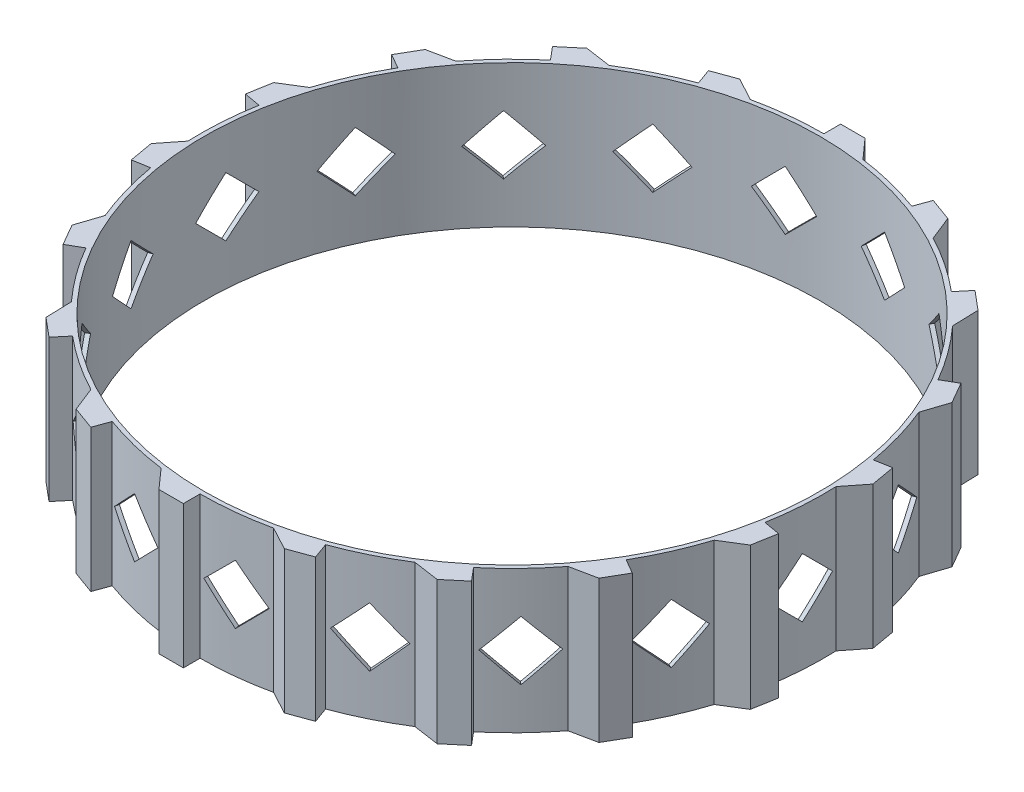
SolidWorks part; units mm, degrees
ref_plane "Front Plane" through (0, 0, 0) normal (0, 0, 1) x (1, 0, 0)
ref_plane "Top Plane" through (0, 0, 0) normal (0, 1, 0) x (1, 0, 0)
ref_plane "Right Plane" through (0, 0, 0) normal (1, 0, 0) x (0, 0, -1)
sketch "Sketch1" plane through (0, 0, 0) normal (0, 1, 0) x (1, 0, 0)
  line L2 (0, 37.25) -> (0, 39.25)
  line L3 (0, 39.25) -> (2.9158, 39.25)
  line L4 (2.9158, 39.25) -> (5, 36.9129)
  line L5 (12.7403, 35.0036) -> (13.4243, 36.8829)
  line L6 (13.4243, 36.8829) -> (16.1643, 35.8857)
  line L7 (16.1643, 35.8857) -> (17.3234, 32.9767)
  line L8 (23.9438, 28.5352) -> (25.2294, 30.0672)
  line L9 (25.2294, 30.0672) -> (27.4631, 28.193)
  line L10 (27.4631, 28.193) -> (27.5574, 25.063)
  line L11 (32.2594, 18.625) -> (33.9915, 19.625)
  line L12 (33.9915, 19.625) -> (35.4494, 17.0998)
  line L13 (35.4494, 17.0998) -> (34.4675, 14.1263)
  line L14 (36.6841, 6.4684) -> (38.6537, 6.8157)
  line L15 (38.6537, 6.8157) -> (39.16, 3.9442)
  line L16 (39.16, 3.9442) -> (37.2204, 1.4858)
  line L17 (36.6841, -6.4684) -> (38.6537, -6.8157)
  line L18 (38.6537, -6.8157) -> (38.1474, -9.6872)
  line L19 (38.1474, -9.6872) -> (35.4839, -11.3339)
  line L20 (32.2594, -18.625) -> (33.9915, -19.625)
  line L21 (33.9915, -19.625) -> (32.5336, -22.1502)
  line L22 (32.5336, -22.1502) -> (29.4675, -22.7866)
  line L23 (23.9438, -28.5352) -> (25.2294, -30.0672)
  line L24 (25.2294, -30.0672) -> (22.9958, -31.9415)
  line L25 (22.9958, -31.9415) -> (19.8969, -31.4909)
  line L26 (12.7403, -35.0036) -> (13.4243, -36.8829)
  line L27 (13.4243, -36.8829) -> (10.6843, -37.8802)
  line L28 (10.6843, -37.8802) -> (7.9265, -36.3969)
  line L29 (0, -37.25) -> (0, -39.25)
  line L30 (0, -39.25) -> (-2.9158, -39.25)
  line L31 (-2.9158, -39.25) -> (-5, -36.9129)
  line L32 (-12.7403, -35.0036) -> (-13.4243, -36.8829)
  line L33 (-13.4243, -36.8829) -> (-16.1643, -35.8857)
  line L34 (-16.1643, -35.8857) -> (-17.3234, -32.9767)
  line L35 (-23.9438, -28.5352) -> (-25.2294, -30.0672)
  line L36 (-25.2294, -30.0672) -> (-27.4631, -28.193)
  line L37 (-27.4631, -28.193) -> (-27.5574, -25.063)
  line L38 (-32.2594, -18.625) -> (-33.9915, -19.625)
  line L39 (-33.9915, -19.625) -> (-35.4494, -17.0998)
  line L40 (-35.4494, -17.0998) -> (-34.4675, -14.1263)
  line L41 (-36.6841, -6.4684) -> (-38.6537, -6.8157)
  line L42 (-38.6537, -6.8157) -> (-39.16, -3.9442)
  line L43 (-39.16, -3.9442) -> (-37.2204, -1.4858)
  line L44 (-36.6841, 6.4684) -> (-38.6537, 6.8157)
  line L45 (-38.6537, 6.8157) -> (-38.1474, 9.6872)
  line L46 (-38.1474, 9.6872) -> (-35.4839, 11.3339)
  line L47 (-32.2594, 18.625) -> (-33.9915, 19.625)
  line L48 (-33.9915, 19.625) -> (-32.5336, 22.1502)
  line L49 (-32.5336, 22.1502) -> (-29.4675, 22.7866)
  line L50 (-23.9438, 28.5352) -> (-25.2294, 30.0672)
  line L51 (-25.2294, 30.0672) -> (-22.9958, 31.9415)
  line L52 (-22.9958, 31.9415) -> (-19.8969, 31.4909)
  line L53 (-12.7403, 35.0036) -> (-13.4243, 36.8829)
  line L54 (-13.4243, 36.8829) -> (-10.6843, 37.8802)
  line L55 (-10.6843, 37.8802) -> (-7.9265, 36.3969)
  circle A0 centre (0, 0) radius 36.75
  arc A1 (-15.0919, 34.0558) -> (-19.8969, 31.4909) centre (0, 0) ccw
  arc A2 (-2.534, 37.1637) -> (-7.9265, 36.3969) centre (0, 0) ccw
  arc A3 (10.3295, 35.7891) -> (5, 36.9129) centre (0, 0) ccw
  arc A4 (21.9472, 30.0979) -> (17.3234, 32.9767) centre (0, 0) ccw
  arc A5 (30.9177, 20.7764) -> (27.5574, 25.063) centre (0, 0) ccw
  arc A6 (36.1591, 8.9489) -> (34.4675, 14.1263) centre (0, 0) ccw
  arc A7 (37.0391, -3.9579) -> (37.2204, 1.4858) centre (0, 0) ccw
  arc A8 (33.4517, -16.3873) -> (35.4839, -11.3339) centre (0, 0) ccw
  arc A9 (25.8295, -26.8402) -> (29.4675, -22.7866) centre (0, 0) ccw
  arc A10 (15.0919, -34.0558) -> (19.8969, -31.4909) centre (0, 0) ccw
  arc A11 (2.534, -37.1637) -> (7.9265, -36.3969) centre (0, 0) ccw
  arc A12 (-10.3295, -35.7891) -> (-5, -36.9129) centre (0, 0) ccw
  arc A13 (-21.9472, -30.0979) -> (-17.3234, -32.9767) centre (0, 0) ccw
  arc A14 (-30.9177, -20.7764) -> (-27.5574, -25.063) centre (0, 0) ccw
  arc A15 (-36.1591, -8.9489) -> (-34.4675, -14.1263) centre (0, 0) ccw
  arc A16 (-37.0391, 3.9579) -> (-37.2204, -1.4858) centre (0, 0) ccw
  arc A17 (-33.4517, 16.3873) -> (-35.4839, 11.3339) centre (0, 0) ccw
  arc A18 (-25.8295, 26.8402) -> (-29.4675, 22.7866) centre (0, 0) ccw
  arc A19 (-2.534, 37.1637) -> (0, 37.25) centre (0, 0) cw
  arc A20 (10.3295, 35.7891) -> (12.7403, 35.0036) centre (0, 0) cw
  arc A21 (21.9472, 30.0979) -> (23.9438, 28.5352) centre (0, 0) cw
  arc A22 (30.9177, 20.7764) -> (32.2594, 18.625) centre (0, 0) cw
  arc A23 (36.1591, 8.9489) -> (36.6841, 6.4684) centre (0, 0) cw
  arc A24 (37.0391, -3.9579) -> (36.6841, -6.4684) centre (0, 0) cw
  arc A25 (33.4517, -16.3873) -> (32.2594, -18.625) centre (0, 0) cw
  arc A26 (25.8295, -26.8402) -> (23.9438, -28.5352) centre (0, 0) cw
  arc A27 (15.0919, -34.0558) -> (12.7403, -35.0036) centre (0, 0) cw
  arc A28 (2.534, -37.1637) -> (0, -37.25) centre (0, 0) cw
  arc A29 (-10.3295, -35.7891) -> (-12.7403, -35.0036) centre (0, 0) cw
  arc A30 (-21.9472, -30.0979) -> (-23.9438, -28.5352) centre (0, 0) cw
  arc A31 (-30.9177, -20.7764) -> (-32.2594, -18.625) centre (0, 0) cw
  arc A32 (-36.1591, -8.9489) -> (-36.6841, -6.4684) centre (0, 0) cw
  arc A33 (-37.0391, 3.9579) -> (-36.6841, 6.4684) centre (0, 0) cw
  arc A34 (-33.4517, 16.3873) -> (-32.2594, 18.625) centre (0, 0) cw
  arc A35 (-25.8295, 26.8402) -> (-23.9438, 28.5352) centre (0, 0) cw
  arc A36 (-15.0919, 34.0558) -> (-12.7403, 35.0036) centre (0, 0) cw
  point P79 (0, 0)
  point P126 (0, 0)
  point P149 (0, 0)
  dimension "D1" = 5
  dimension "D2" = 0.5
  dimension "D3" = 73.5
  dimension "D4" = 2
  dimension "D5" = 2.9158
  dimension "D6" = 18
  dimension "D7" = 18
extrude "Boss-Extrude1" add sketch "Sketch1" along normal blind 17
sketch "Sketch2" plane through (0, 0, 0) normal (1, 0, 0) x (0, 0, -1)
  line L0 (-2.4913, 17) -> (-2.4913, 0)
  line L1 (1.4858, 17) -> (-6.4684, 17) construction
  line L2 (-6.4684, 0) -> (1.4858, 0) construction
  line L3 (-2.4913, 8.5) -> (1.0442, 8.5)
  line L4 (1.0442, 8.5) -> (-2.4913, 12.0355)
  line L5 (1.0442, 8.5) -> (-2.4913, 4.9645)
  line L6 (-6.0268, 8.5) -> (-2.4913, 12.0355)
  line L7 (-6.0268, 8.5) -> (-2.4913, 4.9645)
  dimension "D1" = 90
  dimension "D2" = 5
  dimension "D3" = 45
extrude "Cut-Extrude1" cut sketch "Sketch2" along normal blind 138 contours L6 L7 L0 | L5 L3 L0 | L3 L4 L0 region at (0, 9.6785, 1.3128) region at (0, 8.5, 3.6698) region at (0, 7.3215, 1.3128)
ref_axis "Axis1" through (0, 17, 0) along (0, -1, 0)
pattern_circular "CirPattern1" count 18 over 360 about axis through (0, 17, 0) along (0, -1, 0) of "Cut-Extrude1"
